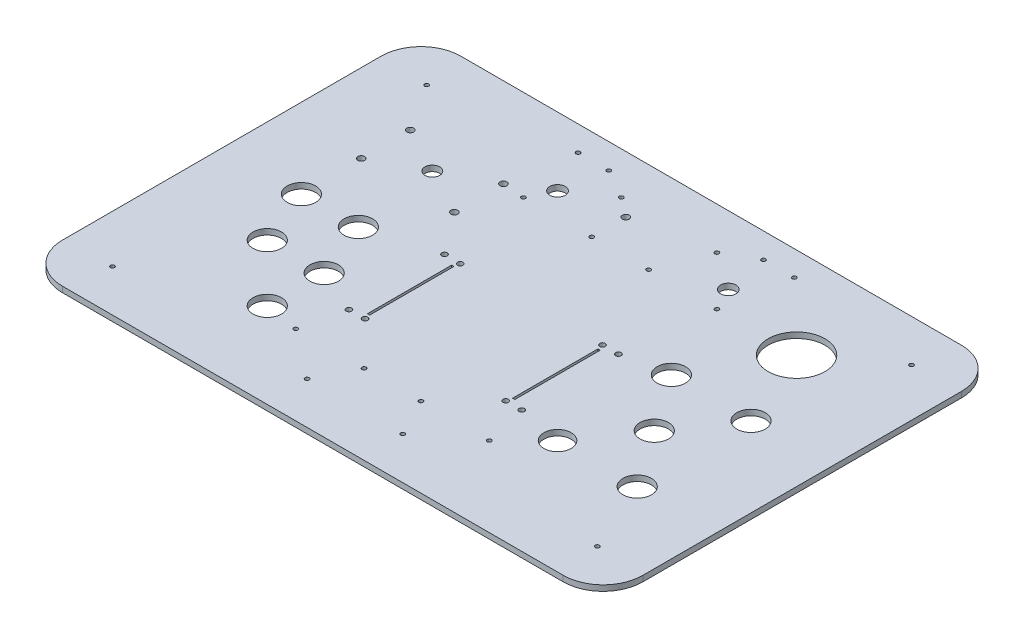
SolidWorks part; units mm, degrees
material "Perspex (TM) GS Acrylic Cast Sheet"
ref_plane "Front Plane" through (0, 0, 0) normal (0, 0, 1) x (1, 0, 0)
ref_plane "Top Plane" through (0, 0, 0) normal (0, 1, 0) x (1, 0, 0)
ref_plane "Right Plane" through (0, 0, 0) normal (1, 0, 0) x (0, 0, -1)
sketch "Sketch1" plane through (0, 0, 0) normal (0, 1, 0) x (1, 0, 0)
  line L1 (0, 0) -> (510, 0)
  line L2 (0, 0) -> (0, 350)
  line L3 (0, 350) -> (510, 350)
  line L4 (510, 0) -> (510, 350)
  dimension "D1" = 510
  dimension "D2" = 350
extrude "Boss-Extrude1" add sketch "Sketch1" along normal blind 5
sketch "Sketch2" plane through (0, 5, 0) normal (0, 1, 0) x (1, 0, 0)
  line L0 (510, 350) -> (0, 350) construction
  line L1 (110, 250) -> (175.8433, 250) construction
  line L2 (110, 250) -> (110, 296.2555) construction
  line L3 (0, 350) -> (0, 0) construction
  circle A0 centre (110, 250) radius 6.5
  circle A2 centre (150.91, 271.59) radius 3
  circle A3 centre (150.91, 228.41) radius 3
  circle A4 centre (69.09, 228.41) radius 3
  circle A5 centre (69.09, 271.59) radius 3
  dimension "D1" = 13
  dimension "D2" = 100
  dimension "D5" = 6
  dimension "D3" = 40.91
  dimension "D4" = 21.59
  dimension "D6" = 110
extrude "1 Joyystick" cut sketch "Sketch2" against normal through all
sketch "Sketch3" plane through (0, 5, 0) normal (0, 1, 0) x (1, 0, 0)
  line L0 (0, 350) -> (0, 0) construction
  line L2 (475, 350) -> (35, 350) construction
  circle A0 centre (70, 175) radius 12.5
  circle A1 centre (120, 175) radius 12.5
  circle A2 centre (90, 125) radius 12.5
  circle A3 centre (140, 125) radius 12.5
  circle A4 centre (140, 75) radius 12.5
  dimension "D1" = 25
  dimension "D2" = 25
  dimension "D3" = 25
  dimension "D4" = 25
  dimension "D5" = 25
  dimension "D11" = 175
  dimension "D6" = 70
  dimension "D7" = 50
  dimension "D8" = 50
  dimension "D9" = 50
  dimension "D10" = 50
  dimension "D12" = 20
extrude "1 Buttons" cut sketch "Sketch3" against normal through all
sketch "Sketch4" plane through (0, 5, 0) normal (0, 1, 0) x (1, 0, 0)
  line L0 (510, 350) -> (0, 350) construction
  line L1 (0, 350) -> (0, 0) construction
  circle A0 centre (180, 290) radius 6.75
  dimension "D1" = 13.5
  dimension "D2" = 60
  dimension "D3" = 180
extrude "1 Rocket Switch" cut sketch "Sketch4" against normal through all
sketch "Sketch5" plane through (0, 5, 0) normal (0, 1, 0) x (1, 0, 0)
  line L0 (192, 150) -> (210.2533, 150) construction
  line L1 (190, 187) -> (192, 187)
  line L2 (190, 187) -> (190, 113)
  line L3 (190, 113) -> (192, 113)
  line L4 (192, 187) -> (192, 113)
  line L5 (190, 150) -> (192, 150) construction
  line L7 (510, 350) -> (0, 350) construction
  line L8 (185.7526, 194.2625) -> (184.4144, 100.0138) construction
  line L9 (0, 350) -> (0, 0) construction
  circle A0 centre (178.7197, 192) radius 2.4
  circle A1 centre (192.7183, 191.8012) radius 2.4
  circle A2 centre (192.7183, 108.1988) radius 2.4
  circle A3 centre (178.7197, 108) radius 2.4
  point P7 (191, 187)
  dimension "D5" = 4.8
  dimension "D1" = 2
  dimension "D2" = 74
  dimension "D3" = 5.35
  dimension "D4" = 190
  dimension "D6" = 7
  dimension "D7" = 200
  dimension "D8" = 5
  dimension "D9" = 4.8012
extrude "1 Potentiometer" cut sketch "Sketch5" against normal through all
fillet "Fillet1" radius 35 4 edges at (0, 2.5, 0) (510, 2.5, 0) (510, 2.5, -350) (0, 2.5, -350)
sketch "Sketch6" plane through (0, 5, 0) normal (0, 1, 0) x (1, 0, 0)
  line L0 (510, 35) -> (510, 315) construction
  line L1 (475, 350) -> (35, 350) construction
  circle A0 centre (440, 200) radius 12.5
  circle A1 centre (370, 200) radius 12.5
  circle A2 centre (440, 100) radius 12.5
  circle A3 centre (370, 100) radius 12
  circle A4 centre (405, 150) radius 12.5
  dimension "D1" = 25
  dimension "D2" = 25
  dimension "D3" = 24
  dimension "D4" = 25
  dimension "D5" = 25
  dimension "D6" = 70
  dimension "D7" = 70
  dimension "D8" = 70
  dimension "D9" = 100
  dimension "D10" = 50
  dimension "D11" = 150
  dimension "D12" = 35
extrude "2 Buttons" cut sketch "Sketch6" against normal through all
sketch "Sketch8" plane through (0, 5, 0) normal (0, 1, 0) x (1, 0, 0)
  line L0 (319, 187.5) -> (319, 112.5) construction
  line L1 (320, 187.5) -> (318, 187.5)
  line L2 (320, 187.5) -> (320, 112.5)
  line L3 (320, 112.5) -> (318, 112.5)
  line L4 (318, 187.5) -> (318, 112.5)
  line L5 (324, 205.9826) -> (324, 86.9169) construction
  line L6 (320, 150) -> (327.2352, 150) construction
  line L8 (510, 35) -> (510, 315) construction
  line L9 (475, 350) -> (35, 350) construction
  circle A0 centre (331, 192.5) radius 2.4
  circle A1 centre (331, 107.5) radius 2.4
  circle A2 centre (317, 107.5) radius 2.4
  circle A3 centre (317, 192.5) radius 2.4
  point P22 (319, 150)
  dimension "D2" = 4.8
  dimension "D3" = 42.5
  dimension "D1" = 5
  dimension "D4" = 1
  dimension "D5" = 2
  dimension "D6" = 190
  dimension "D7" = 200
  dimension "D8" = 7
sketch "Sketch9" plane through (0, 5, 0) normal (0, 1, 0) x (1, 0, 0)
  line L0 (510, 35) -> (510, 315) construction
  line L1 (475, 350) -> (35, 350) construction
  circle A0 centre (410, 270) radius 25
  dimension "D1" = 50
  dimension "D2" = 100
  dimension "D3" = 80
extrude "2 speaker" cut sketch "Sketch9" against normal through all
sketch "Sketch10" plane through (0, 5, 0) normal (0, 1, 0) x (1, 0, 0)
  line L1 (510, 35) -> (510, 315) construction
  line L2 (475, 350) -> (35, 350) construction
  circle A0 centre (330, 290) radius 6.75
  dimension "D1" = 13.5
  dimension "D2" = 60
  dimension "D3" = 180
extrude "2 Rocket Switch" cut sketch "Sketch10" against normal through all
extrude "2 Potentiometer" cut sketch "Sketch8" against normal through all
sketch "Sketch11" plane through (0, 5, 0) normal (0, 1, 0) x (1, 0, 0)
  line L0 (280, 70) -> (280, 268.2) construction
  line L1 (340, 70) -> (340, 270) construction
  line L2 (365.4787, 70) -> (281.3845, 70) construction
  line L3 (356.6021, 270) -> (280, 270) construction
  line L4 (510, 35) -> (510, 315) construction
  line L5 (475, 350) -> (35, 350) construction
  circle A0 centre (340, 70) radius 1.8
  circle A1 centre (280, 70) radius 1.8
  circle A2 centre (280, 270) radius 1.8
  circle A3 centre (340, 270) radius 1.8
  dimension "D1" = 200
  dimension "D3" = 3.6
  dimension "D4" = 3.6
  dimension "D5" = 3.6
  dimension "D6" = 3.6
  dimension "D2" = 60
  dimension "D7" = 170
  dimension "D8" = 80
extrude "2 PCB1" cut sketch "Sketch11" against normal through all
sketch "Sketch12" plane through (0, 5, 0) normal (0, 1, 0) x (1, 0, 0)
  line L0 (159.4963, 70) -> (271.8437, 70) construction
  line L1 (244.3419, 270) -> (170, 270) construction
  line L2 (230, 70) -> (230, 270) construction
  line L3 (170, 30.2464) -> (170, 266.6202) construction
  line L5 (475, 350) -> (35, 350) construction
  line L6 (0, 315) -> (0, 35) construction
  circle A0 centre (230, 70) radius 1.8
  circle A1 centre (170, 70) radius 1.8
  circle A2 centre (230, 270) radius 1.8
  circle A3 centre (170, 270) radius 1.8
  dimension "D3" = 3.6
  dimension "D4" = 3.6
  dimension "D7" = 3.6
  dimension "D8" = 3.6
  dimension "D1" = 200
  dimension "D2" = 60
  dimension "D5" = 170
  dimension "D6" = 80
extrude "1 PCB2" cut sketch "Sketch12" against normal through all
sketch "Sketch13" plane through (0, 5, 0) normal (0, 1, 0) x (1, 0, 0)
  line L0 (475, 350) -> (35, 350) construction
  line L1 (510, 35) -> (510, 315) construction
  circle A0 centre (350, 328) radius 1.8
  circle A1 centre (323, 328) radius 1.8
  dimension "D1" = 3.6
  dimension "D2" = 3.6
  dimension "D3" = 27
  dimension "D4" = 22
  dimension "D5" = 160
extrude "2 USB Connector" cut sketch "Sketch13" against normal through all
sketch "Sketch14" plane through (0, 5, 0) normal (0, 1, 0) x (1, 0, 0)
  line L0 (475, 350) -> (35, 350) construction
  line L1 (0, 315) -> (0, 35) construction
  circle A0 centre (187, 328) radius 1.8
  circle A1 centre (160, 328) radius 1.8
  dimension "D1" = 3.6
  dimension "D2" = 3.6
  dimension "D4" = 22
  dimension "D3" = 27
  dimension "D5" = 160
extrude "1 USB Connector" cut sketch "Sketch14" against normal through all
sketch "Sketch15" plane through (0, 5, 0) normal (0, 1, 0) x (1, 0, 0)
  line L0 (475, 350) -> (35, 350) construction
  line L1 (0, 315) -> (0, 35) construction
  circle A0 centre (230, 300) radius 3
  dimension "D1" = 6
  dimension "D2" = 50
  dimension "D3" = 230
extrude "Power" cut sketch "Sketch15" against normal through all
sketch "Sketch16" plane through (0, 5, 0) normal (0, 1, 0) x (1, 0, 0)
  line L0 (510, 35) -> (510, 315) construction
  line L1 (35, 0) -> (475, 0) construction
  line L2 (255, 0) -> (255, 350) construction
  line L3 (475, 350) -> (35, 350) construction
  circle A0 centre (468, 37) radius 1.8
  circle A1 centre (297, 37) radius 1.8
  circle A2 centre (468, 313) radius 1.8
  circle A3 centre (297, 313) radius 1.8
  circle A4 centre (213, 313) radius 1.8
  circle A5 centre (42, 313) radius 1.8
  circle A6 centre (213, 37) radius 1.8
  circle A7 centre (42, 37) radius 1.8
  dimension "D1" = 42
  dimension "D3" = 3.6
  dimension "D5" = 3.6
  dimension "D8" = 3.6
  dimension "D9" = 3.6
  dimension "D2" = 37
  dimension "D4" = 171
  dimension "D6" = 276
  dimension "D7" = 276
extrude "LED fixings" cut sketch "Sketch16" against normal through all
